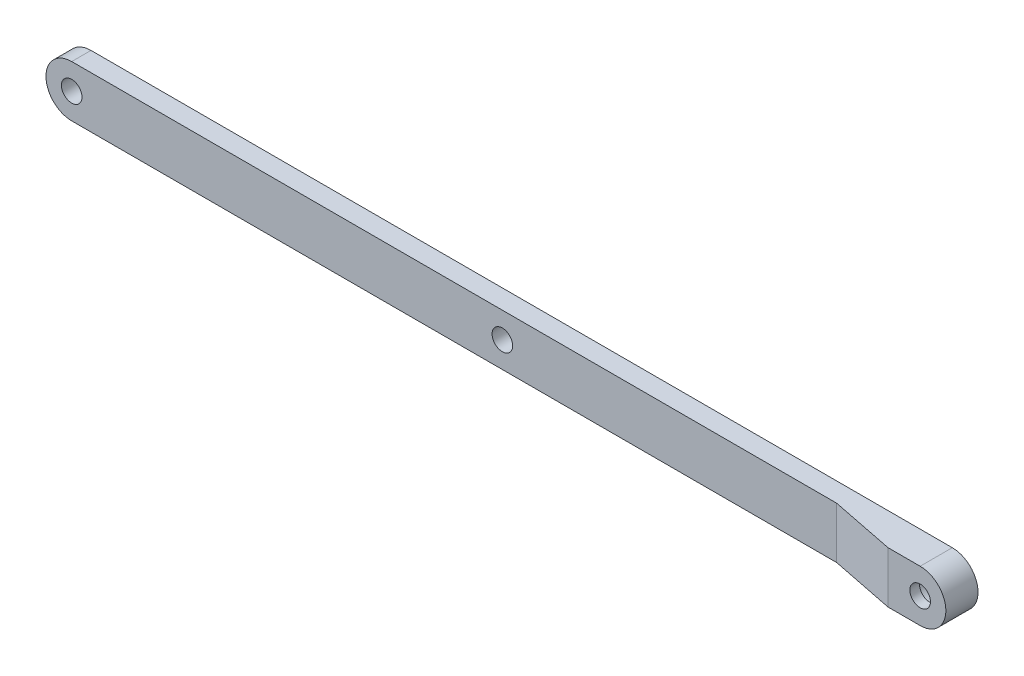
SolidWorks part; units mm, degrees
ref_plane "前基準面" through (0, 0, 0) normal (0, 0, 1) x (1, 0, 0)
ref_plane "上基準面" through (0, 0, 0) normal (0, 1, 0) x (1, 0, 0)
ref_plane "右基準面" through (0, 0, 0) normal (1, 0, 0) x (0, 0, -1)
sketch "草圖1" plane through (0, 0, 0) normal (0, 0, 1) x (1, 0, 0)
  line L0 (-53.1113, 0) -> (80.8887, 0) construction
  line L1 (-53.1113, 4) -> (80.8887, 4)
  line L2 (-53.1113, -4) -> (80.8887, -4)
  arc A0 (-53.1113, 4) -> (-53.1113, -4) centre (-53.1113, 0) ccw
  arc A1 (80.8887, -4) -> (80.8887, 4) centre (80.8887, 0) ccw
  circle A2 centre (80.8887, 0) radius 2.75
  circle A3 centre (-53.1113, 0) radius 1.6
  circle A4 centre (13.8887, 0) radius 1.6
  point P3 (13.8887, 0)
  dimension "D2" = 4
  dimension "D3" = 3.2
  dimension "D4" = 5.5
  dimension "D5" = 3.2
  dimension "D1" = 134
extrude "填料-伸長1" add sketch "草圖1" along normal blind 5
sketch "草圖2" plane through (0, 0, 5) normal (0, 0, 1) x (1, 0, 0)
  circle A0 centre (80.8887, 0) radius 2.75
  circle A1 centre (80.8887, 0) radius 1.6
  dimension "D1" = 3.2
extrude "填料-伸長2" add sketch "草圖2" against normal blind 1.5
sketch "草圖3" plane through (0, 0, 5) normal (0, 0, 1) x (1, 0, 0)
  line L0 (65.8887, 4) -> (65.8887, -4)
  line L1 (65.8887, 4) -> (-61.1113, 4)
  line L2 (65.8887, -4) -> (-61.1113, -4)
  line L3 (-61.1113, 4) -> (-61.1113, -4)
  line L4 (80.8887, 4) -> (-53.1113, 4) construction
  line L5 (-53.1113, -4) -> (80.8887, -4) construction
  circle A0 centre (-53.1113, 0) radius 1.6 construction
  circle A1 centre (80.8887, 0) radius 1.6 construction
  dimension "D1" = 8
  dimension "D2" = 15
extrude "除料-伸長1" cut sketch "草圖3" against normal blind 2
chamfer "導角1" distance 10 distance2 2 1 edges at (65.8887, 0, 5) first distance on face at (74.3887, 0, 5)
